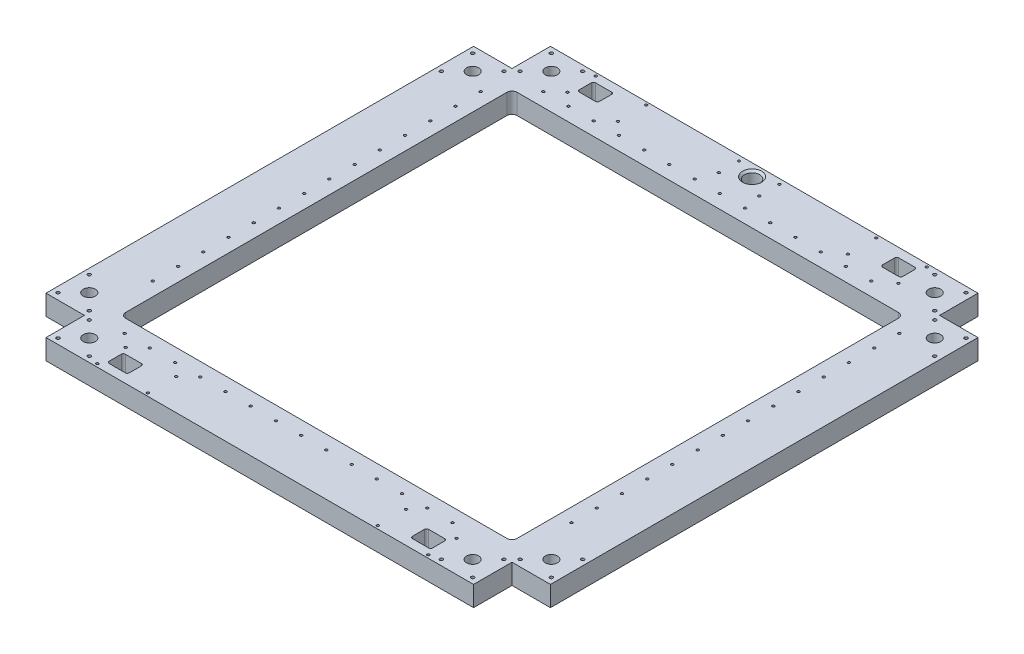
SolidWorks part; units mm, degrees
material "ASTM A36 Steel"
ref_plane "Front Plane" through (0, 0, 0) normal (0, 0, 1) x (1, 0, 0)
ref_plane "Top Plane" through (0, 0, 0) normal (0, 1, 0) x (1, 0, 0)
ref_plane "Right Plane" through (0, 0, 0) normal (1, 0, 0) x (0, 0, -1)
sketch "Sketch1" plane through (0, 0, 0) normal (0, 1, 0) x (1, 0, 0)
  line L1 (250, -250) -> (-250, -250)
  line L2 (250, -250) -> (250, 250)
  line L3 (250, 250) -> (-250, 250)
  line L4 (-250, -250) -> (-250, 250)
  line L5 (250, -250) -> (-250, 250) construction
  line L6 (250, 250) -> (-250, -250) construction
  point P0 (0, 0)
  dimension "D1" = 500
  dimension "D2" = 500
extrude "Boss-Extrude1" add sketch "Sketch1" along normal blind 20
sketch "Sketch2" plane through (0, 20, 0) normal (0, 1, 0) x (1, 0, 0)
  line L0 (250, 250) -> (-250, 250) construction
  line L10 (-250, 250) -> (-250, -250) construction
  line L15 (-250, 169) -> (-208, 169)
  line L16 (-250, 169) -> (-250, 211)
  line L17 (-174.5, 213.5) -> (-205.5, 213.5)
  line L27 (-250, 211) -> (-208, 211)
  line L33 (-208, 169) -> (-208, 211)
  line L35 (-250, 169) -> (-208, 211) construction
  line L36 (-250, 211) -> (-208, 169) construction
  line L37 (-169, 208) -> (-211, 208)
  line L38 (-169, 208) -> (-169, 250)
  line L39 (-169, 250) -> (-211, 250)
  line L40 (-211, 208) -> (-211, 250)
  line L41 (-169, 208) -> (-211, 250) construction
  line L42 (-169, 250) -> (-211, 208) construction
  line L43 (-208, 206) -> (-213, 211)
  line L44 (-174.5, 213.5) -> (-174.5, 244.5)
  line L45 (-174.5, 244.5) -> (-205.5, 244.5)
  line L46 (-205.5, 213.5) -> (-205.5, 244.5)
  line L47 (-174.5, 213.5) -> (-205.5, 244.5) construction
  line L48 (-174.5, 244.5) -> (-205.5, 213.5) construction
  line L49 (-213.5, 174.5) -> (-244.5, 174.5)
  line L50 (-213.5, 174.5) -> (-213.5, 205.5)
  line L51 (-213.5, 205.5) -> (-244.5, 205.5)
  line L52 (-244.5, 174.5) -> (-244.5, 205.5)
  line L53 (-213.5, 174.5) -> (-244.5, 205.5) construction
  line L54 (-213.5, 205.5) -> (-244.5, 174.5) construction
  line L55 (-206, 208) -> (-211, 213)
  line L56 (-213, 211) -> (-211, 213) construction
  point P1 (-229, 190)
  point P5 (-190, 229)
  point P23 (-229, 190)
  point P27 (-190, 229)
  dimension "D1" = 5
  dimension "D2" = 45
  dimension "D3" = 42
  dimension "D4" = 31
  dimension "D5" = 45
  dimension "D6" = 5
  dimension "D7" = 60
hole_wizard "Bearing Press Fit" positions "Sketch8" profile "Sketch9" hole size "Ø12.0" standard "ANSI Metric" end condition through all
sketch "Sketch8" plane through (0, 20, 0) normal (0, 1, 0) x (1, 0, 0)
  line L1 (-169, 250) -> (-211, 208) construction
  point P8 (-190, 229)
  point P12 (-229, 190)
sketch "Sketch9" plane through (-190, 20, -229) normal (1, 0, 0) x (0, 0, 1)
  line L0 (0, 0) -> (0, 20)
  line L1 (0, 20) -> (6, 20)
  line L2 (6, 20) -> (6, 0)
  line L5 (6, 0) -> (0, 0)
  line L11 (0, -6.35) -> (0, 107.95) construction
  dimension "Thru Hole Dia." = 12
  dimension "Thru Hole Depth" = 20
ref_axis "Axis1" through (0, 21, 0) along (0, -1, 0)
pattern_circular "CirPattern1" count 4 over 360 about axis through (0, 21, 0) along (0, -1, 0) of "Bearing Press Fit"
sketch "Sketch5" plane through (0, 20, 0) normal (0, 1, 0) x (1, 0, 0)
  line L1 (194, -194) -> (-194, -194)
  line L2 (194, -194) -> (194, 194)
  line L3 (194, 194) -> (-194, 194)
  line L4 (-194, -194) -> (-194, 194)
  line L5 (194, -194) -> (-194, 194) construction
  line L6 (194, 194) -> (-194, -194) construction
  point P0 (0, 0)
  dimension "D1" = 388
extrude "Cut-Extrude1" cut sketch "Sketch5" against normal up to surface (20 mm away) up to face at (-229, 0, 196)
sketch "Sketch10" plane through (0, 0, 0) normal (0, 1, 0) x (1, 0, 0)
  line L5 (194, 194) -> (-194, 194) construction
  line L6 (214, -214) -> (-214, -214)
  line L14 (214, -214) -> (214, 214)
  line L15 (214, 214) -> (-214, 214)
  line L16 (-214, -214) -> (-214, 214)
  line L17 (214, -214) -> (-214, 214) construction
  line L18 (214, 214) -> (-214, -214) construction
  line L19 (201.5, -201.5) -> (-201.5, -201.5)
  line L20 (201.5, -201.5) -> (201.5, 201.5)
  line L21 (201.5, 201.5) -> (-201.5, 201.5)
  line L22 (-201.5, -201.5) -> (-201.5, 201.5)
  line L23 (201.5, -201.5) -> (-201.5, 201.5) construction
  line L24 (201.5, 201.5) -> (-201.5, -201.5) construction
  point P0 (0, 0)
  point P6 (0, 0)
  dimension "D2" = 7.5
  dimension "D1" = 12.5
extrude "Linear Rail Slot" cut sketch "Sketch10" along normal blind 2.5
fillet "Fillet2" radius 5 4 edges at (-194, 10, 194) (194, 10, 194) (194, 10, -194) (-194, 10, -194)
sketch "Sketch11" plane through (0, 2.5, 0) normal (0, -1, 0) x (1, 0, 0)
  line L0 (-194, 207.5) -> (166, 207.5)
  line L1 (-201.5, 201.5) -> (201.5, 201.5) construction
  line L3 (-214, -214) -> (-214, 214) construction
  point P16 (148.5, 207.5)
  point P18 (123.5, 207.5)
  point P19 (98.5, 207.5)
  point P20 (73.5, 207.5)
  point P21 (48.5, 207.5)
  point P22 (23.5, 207.5)
  point P23 (-1.5, 207.5)
  point P24 (-26.5, 207.5)
  point P25 (-51.5, 207.5)
  point P26 (-76.5, 207.5)
  point P28 (-101.5, 207.5)
  point P29 (-126.5, 207.5)
  point P30 (-151.5, 207.5)
  point P31 (-176.5, 207.5)
  dimension "D1" = 360
  dimension "D2" = 6
  dimension "D4" = 14
  dimension "D5" = 25
  dimension "D6" = 20
  dimension "D3" = 17.5
hole_wizard "Tap Drill for M3x0.5 Tap1" positions "Sketch12" profile "Sketch13" hole size "M3x0.5" standard "ANSI Metric" end condition through all
sketch "Sketch12" plane through (0, 2.5, 0) normal (0, -1, 0) x (-1, 0, 0)
  line L0 (194, -207.5) -> (-166, -207.5) construction
  point P28 (-148.5, -207.5)
  point P31 (-123.5, -207.5)
  point P34 (-98.5, -207.5)
  point P37 (-73.5, -207.5)
  point P40 (-48.5, -207.5)
  point P43 (-23.5, -207.5)
  point P46 (1.5, -207.5)
  point P49 (26.5, -207.5)
  point P51 (51.5, -207.5)
  point P54 (76.5, -207.5)
  point P57 (101.5, -207.5)
  point P61 (126.5, -207.5)
  point P64 (151.5, -207.5)
  point P67 (176.5, -207.5)
sketch "Sketch13" plane through (148.5, 2.5, 207.5) normal (1, 0, 0) x (0, 0, -1)
  line L0 (0, 0) -> (0, 17.5)
  line L1 (0, 17.5) -> (1.25, 17.5)
  line L2 (1.25, 17.5) -> (1.25, 0)
  line L5 (1.25, 0) -> (0, 0)
  line L11 (0, -6.35) -> (0, 107.95) construction
  dimension "Thru Hole Dia." = 2.5
  dimension "Thru Hole Depth" = 17.5
sketch "Sketch14" plane through (0, 0, 0) normal (0, -1, 0) x (1, 0, 0)
  line L1 (-151.5, 213.5) -> (-176.5, 213.5)
  line L2 (-147.5, 217.5) -> (-147.5, 219.5)
  line L3 (-151.5, 223.5) -> (-176.5, 223.5)
  line L4 (-180.5, 217.5) -> (-180.5, 219.5)
  line L5 (-147.5, 213.5) -> (-180.5, 223.5) construction
  line L6 (-147.5, 223.5) -> (-180.5, 213.5) construction
  line L7 (-201.5, 201.5) -> (201.5, 201.5) construction
  line L8 (-176.5, 207.5) -> (-151.5, 207.5) construction
  line L19 (-1.5, 213.5) -> (-26.5, 213.5)
  line L25 (2.5, 217.5) -> (2.5, 219.5)
  line L26 (-1.5, 223.5) -> (-26.5, 223.5)
  line L31 (-30.5, 217.5) -> (-30.5, 219.5)
  line L32 (2.5, 213.5) -> (-30.5, 223.5) construction
  line L33 (2.5, 223.5) -> (-30.5, 213.5) construction
  line L34 (-26.5, 207.5) -> (-1.5, 207.5) construction
  line L35 (148.5, 213.5) -> (123.5, 213.5)
  line L36 (152.5, 217.5) -> (152.5, 219.5)
  line L37 (148.5, 223.5) -> (123.5, 223.5)
  line L38 (119.5, 217.5) -> (119.5, 219.5)
  line L39 (152.5, 213.5) -> (119.5, 223.5) construction
  line L40 (152.5, 223.5) -> (119.5, 213.5) construction
  line L41 (123.5, 207.5) -> (148.5, 207.5) construction
  arc A3 (-147.5, 219.5) -> (-151.5, 223.5) centre (-151.5, 219.5) ccw
  arc A4 (-151.5, 213.5) -> (-147.5, 217.5) centre (-151.5, 217.5) ccw
  arc A5 (-176.5, 213.5) -> (-180.5, 217.5) centre (-176.5, 217.5) cw
  arc A6 (-176.5, 223.5) -> (-180.5, 219.5) centre (-176.5, 219.5) ccw
  arc A7 (2.5, 219.5) -> (-1.5, 223.5) centre (-1.5, 219.5) ccw
  arc A8 (-1.5, 213.5) -> (2.5, 217.5) centre (-1.5, 217.5) ccw
  arc A9 (-26.5, 213.5) -> (-30.5, 217.5) centre (-26.5, 217.5) cw
  arc A10 (-26.5, 223.5) -> (-30.5, 219.5) centre (-26.5, 219.5) ccw
  arc A11 (152.5, 219.5) -> (148.5, 223.5) centre (148.5, 219.5) ccw
  arc A12 (148.5, 213.5) -> (152.5, 217.5) centre (148.5, 217.5) ccw
  arc A13 (123.5, 213.5) -> (119.5, 217.5) centre (123.5, 217.5) cw
  arc A14 (123.5, 223.5) -> (119.5, 219.5) centre (123.5, 219.5) ccw
  point P0 (-164, 218.5)
  point P12 (-164, 207.5)
  point P26 (-14, 218.5)
  point P45 (136, 218.5)
  dimension "D5" = 3
  dimension "D4" = 4
  dimension "D1" = 33
  dimension "D2" = 12
  dimension "D3" = 10
  dimension "D7" = 25
  dimension "D6" = 150
mirror "Mirror5" about plane through (0, 0, 0) normal (0, 0, 1) of "Tap Drill for M3x0.5 Tap1"
ref_plane "Plane1" through (0, 0, 0) normal (-0.7071, 0, 0.7071) x (0.7071, 0, 0.7071)
mirror "Mirror6" about plane through (0, 0, 0) normal (-0.7071, 0, 0.7071) of "Mirror5"
sketch "Sketch19" plane through (0, 2.5, 0) normal (0, -1, 0) x (1, 0, 0)
  line L0 (-198.5, 201.5) -> (-198.5, 214)
  line L1 (-201.5, 201.5) -> (201.5, 201.5) construction
  line L2 (-214, 214) -> (214, 214) construction
  line L3 (-198.5, 214) -> (-214, 214)
  line L4 (-214, 214) -> (-214, 198.5)
  line L5 (-214, -214) -> (-214, 214) construction
  line L6 (-214, 198.5) -> (-201.5, 198.5)
  line L7 (-201.5, -201.5) -> (-201.5, 201.5) construction
  line L8 (-201.5, 198.5) -> (-201.5, 201.5)
  line L9 (-201.5, 201.5) -> (-198.5, 201.5)
  dimension "D1" = 3
extrude "Boss-Extrude2" add sketch "Sketch19" along normal up to surface (2.5 mm away) up to face at (-229, 0, 196)
pattern_circular "CirPattern4" count 4 over 360 about axis through (0, 21, 0) along (0, -1, 0) of "Boss-Extrude2"
sketch "Sketch20" plane through (0, 20, 0) normal (0, 1, 0) x (1, 0, 0)
  line L5 (-250, -250) -> (250, -250) construction
  line L20 (140.3, -225) -> (160.3, -241) construction
  line L23 (160.3, -225) -> (140.3, -241) construction
  line L28 (114, -247) -> (164, -219) construction
  line L29 (164, -247) -> (114, -219) construction
  line L30 (164, -219) -> (114, -219) construction
  line L31 (114, -247) -> (114, -219) construction
  line L32 (164, -247) -> (114, -247) construction
  line L33 (164, -247) -> (164, -219) construction
  line L34 (158.3, -241) -> (142.3, -241)
  line L35 (140.3, -227) -> (140.3, -239)
  line L36 (158.3, -225) -> (142.3, -225)
  line L37 (160.3, -227) -> (160.3, -239)
  arc A12 (142.3, -225) -> (140.3, -227) centre (142.3, -227) ccw
  arc A13 (140.3, -239) -> (142.3, -241) centre (142.3, -239) ccw
  arc A14 (160.3, -239) -> (158.3, -241) centre (158.3, -239) cw
  arc A15 (160.3, -227) -> (158.3, -225) centre (158.3, -227) ccw
  circle A16 centre (190, -229) radius 6 construction
  point P65 (150.3, -233)
  point P66 (139, -233)
  point P67 (139, -233)
  dimension "D7" = 39.7
  dimension "D8" = 11.3
  dimension "D6" = 2
  dimension "D1" = 28
  dimension "D2" = 50
  dimension "D3" = 17
  dimension "D4" = 20
  dimension "D5" = 16
extrude "Cut-Extrude3" cut sketch "Sketch20" against normal through all
hole_wizard "Tap Drill for M3x0.5 Tap3" positions "Sketch28" profile "Sketch29" hole size "M3x0.5" standard "ANSI Metric" end condition through all
sketch "Sketch28" plane through (0, 20, 0) normal (0, 1, 0) x (1, 0, 0)
  point P0 (164, -219)
  point P3 (164, -247)
  point P6 (114, -247)
  point P8 (114, -219)
sketch "Sketch29" plane through (164, 20, 219) normal (1, 0, 0) x (0, 0, 1)
  line L0 (0, 0) -> (0, 20)
  line L1 (0, 20) -> (1.25, 20)
  line L2 (1.25, 20) -> (1.25, 0)
  line L5 (1.25, 0) -> (0, 0)
  line L11 (0, -6.35) -> (0, 107.95) construction
  dimension "Thru Hole Dia." = 2.5
  dimension "Thru Hole Depth" = 20
mirror "Mirror8" about plane through (0, 0, 0) normal (1, 0, 0) of "Tap Drill for M3x0.5 Tap3", "Cut-Extrude3"
mirror "Mirror9" about plane through (0, 0, 0) normal (0, 0, 1) of "Mirror8"
sketch "Sketch24" plane through (0, 20, 0) normal (0, 1, 0) x (1, 0, 0)
  line L1 (244.5, -205.5) -> (213.5, -205.5)
  line L2 (244.5, -205.5) -> (244.5, -174.5)
  line L3 (244.5, -174.5) -> (213.5, -174.5)
  line L4 (213.5, -205.5) -> (213.5, -174.5)
  line L5 (244.5, -205.5) -> (213.5, -174.5) construction
  line L6 (244.5, -174.5) -> (213.5, -205.5) construction
  line L7 (205.5, -244.5) -> (174.5, -244.5)
  line L8 (205.5, -244.5) -> (205.5, -213.5)
  line L9 (205.5, -213.5) -> (174.5, -213.5)
  line L10 (174.5, -244.5) -> (174.5, -213.5)
  line L11 (205.5, -244.5) -> (174.5, -213.5) construction
  line L12 (205.5, -213.5) -> (174.5, -244.5) construction
  point P0 (229, -190)
  point P6 (190, -229)
  dimension "D1" = 31
hole_wizard "M3 Clearance Hole1" positions "Sketch25" profile "Sketch26" hole size "M3" standard "ANSI Metric" end condition through all
sketch "Sketch25" plane through (0, 20, 0) normal (0, 1, 0) x (1, 0, 0)
  point P0 (205.5, -244.5)
  point P3 (205.5, -213.5)
  point P9 (174.5, -244.5)
  point P12 (213.5, -205.5)
  point P18 (244.5, -174.5)
  point P21 (244.5, -205.5)
sketch "Sketch26" plane through (205.5, 20, 244.5) normal (1, 0, 0) x (0, 0, 1)
  line L0 (0, 0) -> (0, 20)
  line L1 (0, 20) -> (1.6, 20)
  line L2 (1.6, 20) -> (1.6, 0)
  line L5 (1.6, 0) -> (0, 0)
  line L11 (0, -6.35) -> (0, 107.95) construction
  dimension "Thru Hole Dia." = 3.2
  dimension "Thru Hole Depth" = 20
sketch "Sketch27" plane through (0, 20, 0) normal (0, 1, 0) x (1, 0, 0)
  line L1 (250, -250) -> (211.9, -250)
  line L2 (250, -250) -> (250, -211.9)
  line L3 (250, -211.9) -> (211.9, -211.9)
  line L4 (211.9, -250) -> (211.9, -211.9)
  dimension "D1" = 38.1
extrude "Cut-Extrude4" cut sketch "Sketch27" against normal up to surface (20 mm away) up to face at (205.5, 0, 246.1)
pattern_circular "CirPattern3" count 4 over 360 about axis through (0, 21, 0) along (0, -1, 0) of "Cut-Extrude4", "M3 Clearance Hole1"
fillet "Fillet5" radius 4 16 edges at (198.5, 1.25, 214) (198.5, 1.25, 201.5) (201.5, 1.25, 198.5) (214, 1.25, 198.5) (-214, 1.25, 198.5) (-198.5, 1.25, 214) (-201.5, 1.25, 198.5) (-198.5, 1.25, 201.5) (-214, 1.25, -198.5) (-198.5, 1.25, -214) (-198.5, 1.25, -201.5) (-201.5, 1.25, -198.5) (198.5, 1.25, -201.5) (198.5, 1.25, -214) (201.5, 1.25, -198.5) (214, 1.25, -198.5)
hole_wizard "Tap Drill for M3x0.5 Tap4" positions "Sketch35" profile "Sketch36" hole size "M3x0.5" standard "ANSI Metric" end condition up to next
sketch "Sketch35" plane through (0, 20, 0) normal (0, 1, 0) x (1, 0, 0)
  line L1 (20, 225) -> (-20, 225)
  line L2 (20, 225) -> (20, 245)
  line L3 (20, 245) -> (-20, 245)
  line L4 (-20, 225) -> (-20, 245)
  line L5 (20, 225) -> (-20, 245) construction
  line L6 (20, 245) -> (-20, 225) construction
  line L7 (211.9, 250) -> (-211.9, 250) construction
  point P2 (-20, 245)
  point P53 (20, 225)
  point P54 (20, 245)
  point P55 (-20, 225)
  point P69 (0, 235)
  dimension "D1" = 20
  dimension "D2" = 40
  dimension "D3" = 15
sketch "Sketch36" plane through (-20, 20, -245) normal (1, 0, 0) x (0, 0, 1)
  line L0 (0, 0) -> (0, 20)
  line L1 (0, 20) -> (1.25, 20)
  line L2 (1.25, 20) -> (1.25, 0)
  line L5 (1.25, 0) -> (0, 0)
  line L11 (0, -6.35) -> (0, 107.95) construction
  dimension "Thru Hole Dia." = 2.5
  dimension "Thru Hole Depth" = 20
hole_wizard "Ø15.0 (15) Diameter Hole2" positions "Sketch37" profile "Sketch38" hole size "Ø15.0" standard "ANSI Metric" end condition up to next
sketch "Sketch37" plane through (0, 20, 0) normal (0, 1, 0) x (1, 0, 0)
  circle A0 centre (0, 235) radius 1.25 construction
  point P0 (0, 238)
  dimension "D1" = 3
sketch "Sketch38" plane through (0, 20, -238) normal (1, 0, 0) x (0, 0, 1)
  line L0 (0, 0) -> (0, 20)
  line L1 (0, 20) -> (7.5, 20)
  line L2 (7.5, 20) -> (7.5, 0)
  line L5 (7.5, 0) -> (0, 0)
  line L11 (0, -6.35) -> (0, 107.95) construction
  dimension "Thru Hole Dia." = 15
  dimension "Thru Hole Depth" = 20
chamfer "Chamfer1" distance 2 angle 45 2 edges at (0, 0, -230.5) (0, 20, -230.5)
